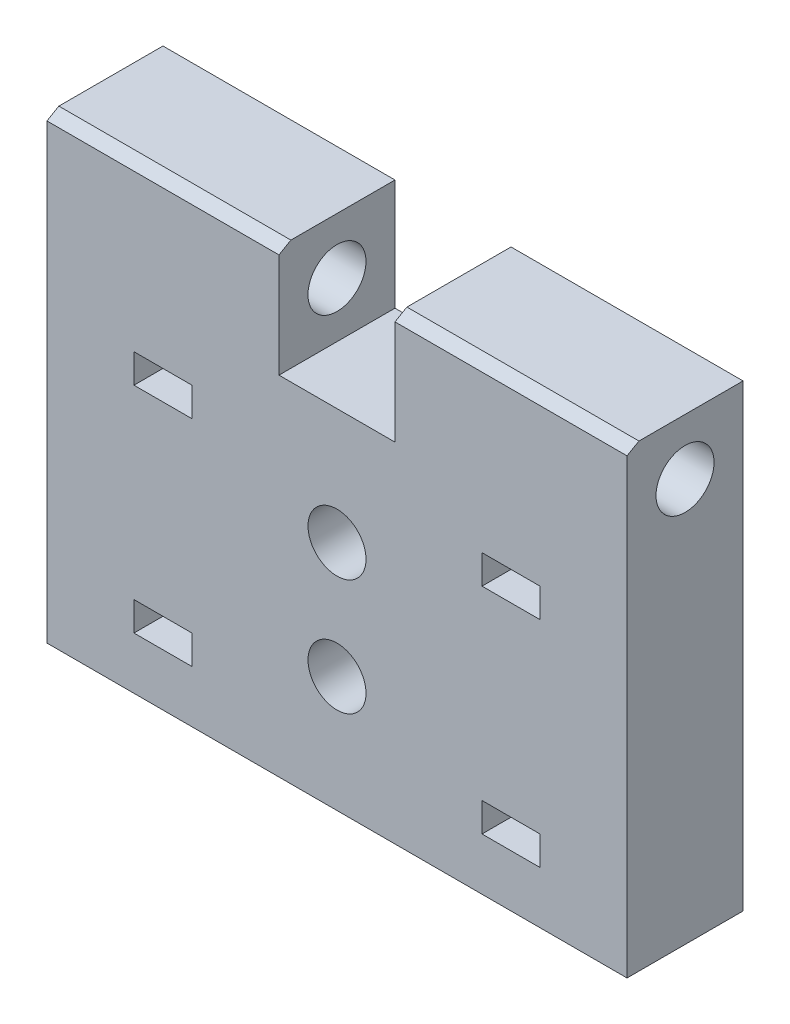
SolidWorks part; units mm, degrees
ref_plane "Plan de face" through (0, 0, 0) normal (0, 0, 1) x (1, 0, 0)
ref_plane "Plan de dessus" through (0, 0, 0) normal (0, 1, 0) x (1, 0, 0)
ref_plane "Plan de droite" through (0, 0, 0) normal (1, 0, 0) x (0, 0, -1)
sketch "Esquisse1" plane through (0, 0, 0) normal (0, 0, 1) x (1, 0, 0)
  line L0 (-25, -15) -> (-5, -15)
  line L1 (-5, -15) -> (5, -15)
  line L2 (0, -15) -> (0, 15) construction
  line L3 (-5, 15) -> (5, 15)
  line L4 (25, -15) -> (25, 29.75)
  line L5 (-5, -15) -> (5, 15) construction
  line L6 (-5, 15) -> (5, -15) construction
  line L7 (5, 29.75) -> (25, 29.75)
  line L8 (-5, 15) -> (-5, 29.75)
  line L9 (-5, 29.75) -> (-25, 29.75)
  line L10 (-25, -15) -> (-25, 29.75)
  line L11 (5, 15) -> (5, 29.75)
  line L12 (25, -15) -> (5, -15)
  circle A0 centre (0, -5) radius 2.5
  circle A1 centre (0, 5) radius 2.5
  point P0 (0, 3.5555)
  dimension "D3" = 10
  dimension "D4" = 5
  dimension "D11" = 5
  dimension "D1" = 30
  dimension "D2" = 10
  dimension "D5" = 5
  dimension "D6" = 20
extrude "Boss.-Extru.1" add sketch "Esquisse1" along normal blind 10 contours L10 L8 L9 | L1 L3 A1 region at (-24.329, 7.375, 0)
sketch "Esquisse2" plane through (-25, 0, 0) normal (-1, 0, 0) x (0, 0, 1)
  line L0 (0, 29.75) -> (10, 29.75)
  line L1 (10, 29.75) -> (10, 23.9765)
  line L2 (10, -15) -> (10, 29.75) construction
  line L3 (10, 23.9765) -> (0, 29.75)
  line L4 (0, 29.75) -> (10, 9.75) construction
  line L5 (10, -15) -> (10, 29.75) construction
  circle A0 centre (5, 19.75) radius 2.5
  dimension "D2" = 5
  dimension "D1" = 30
  dimension "D3" = 10
extrude "Enlèv. mat.-Extru.1" cut sketch "Esquisse2" against normal up to surface (50 mm away) up to face at (25, 7.375, 5)
sketch "Esquisse3" plane through (0, 0, 10) normal (0, 0, 1) x (1, 0, 0)
  line L0 (-5, 15) -> (-5, -15) construction
  line L1 (25, -15) -> (-25, -15) construction
  line L2 (-5, -15) -> (-25, 23.9765) construction
  line L3 (-25, 23.9765) -> (-15, 23.9765) construction
  line L4 (-5, 23.9765) -> (-25, 23.9765) construction
  line L5 (-15, 23.9765) -> (-15, -15) construction
  line L6 (-17.5, 10.5) -> (-12.5, -10.5) construction
  line L7 (-17.5, 8) -> (-12.5, 8)
  line L8 (-17.5, 8) -> (-17.5, 10.5)
  line L9 (-17.5, 10.5) -> (-12.5, 10.5)
  line L10 (-12.5, 8) -> (-12.5, 10.5)
  line L11 (-17.5, 8) -> (-12.5, 10.5) construction
  line L12 (-17.5, 10.5) -> (-12.5, 8) construction
  line L13 (-17.5, -10.5) -> (-12.5, -10.5)
  line L14 (-17.5, -10.5) -> (-17.5, -8)
  line L15 (-17.5, -8) -> (-12.5, -8)
  line L16 (-12.5, -10.5) -> (-12.5, -8)
  line L17 (-17.5, -10.5) -> (-12.5, -8) construction
  line L18 (-17.5, -8) -> (-12.5, -10.5) construction
  line L19 (-17.5, -10.5) -> (-12.5, 10.5) construction
  line L20 (0, 5) -> (0, -5) construction
  line L21 (0, -5) -> (0, 0) construction
  line L22 (0, 0) -> (-15, 0) construction
  line L23 (17.5, -10.5) -> (12.5, 10.5) construction
  line L24 (17.5, -8) -> (12.5, -10.5) construction
  line L25 (17.5, -10.5) -> (12.5, -8) construction
  line L26 (17.5, 10.5) -> (12.5, 8) construction
  line L27 (17.5, 8) -> (12.5, 10.5) construction
  line L28 (17.5, 10.5) -> (12.5, -10.5) construction
  line L29 (12.5, -10.5) -> (12.5, -8)
  line L30 (17.5, -8) -> (12.5, -8)
  line L31 (17.5, -10.5) -> (17.5, -8)
  line L32 (17.5, -10.5) -> (12.5, -10.5)
  line L33 (12.5, 8) -> (12.5, 10.5)
  line L34 (17.5, 10.5) -> (12.5, 10.5)
  line L35 (17.5, 8) -> (17.5, 10.5)
  line L36 (17.5, 8) -> (12.5, 8)
  point P11 (-15, 9.25)
  point P16 (-15, -9.25)
  point P21 (0, 5)
  point P22 (0, -5)
  point P38 (15, -9.25)
  point P39 (15, 9.25)
  dimension "D1" = 2.5
  dimension "D2" = 5
  dimension "D3" = 2.5
  dimension "D4" = 5
  dimension "D5" = 8
extrude "Enlèv. mat.-Extru.2" cut sketch "Esquisse3" against normal up to surface (10 mm away) up to face at (2.5, 5, 0)
sketch "Esquisse4" plane through (-25, 0, 0) normal (-1, 0, 0) x (0, 0, 1)
  line L0 (8.9728, 24.5695) -> (0, 24.5695)
  line L1 (0, 29.75) -> (10, 23.9765) construction
  line L2 (0, -15) -> (0, 29.75) construction
  line L3 (0, 24.5695) -> (0, 29.75)
  line L4 (0, 29.75) -> (8.9728, 29.75)
  line L5 (8.9728, 29.75) -> (8.9728, 24.5695)
extrude "Enlèv. mat.-Extru.3" cut sketch "Esquisse4" against normal blind 50
